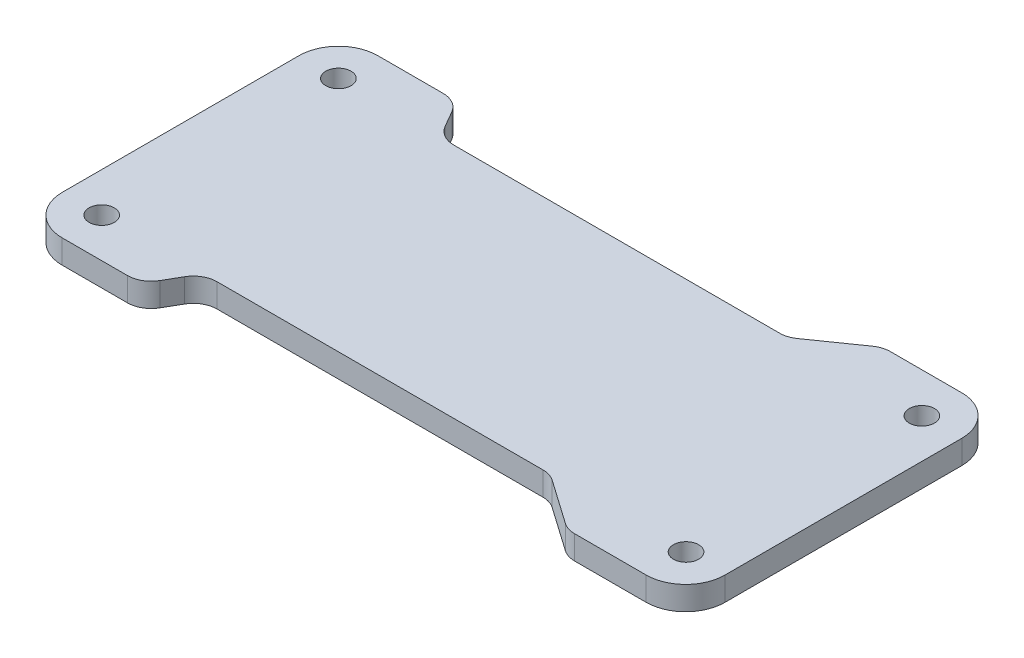
SolidWorks part; units mm, degrees
ref_plane "Front Plane" through (0, 0, 0) normal (0, 0, 1) x (1, 0, 0)
ref_plane "Top Plane" through (0, 0, 0) normal (0, 1, 0) x (1, 0, 0)
ref_plane "Right Plane" through (0, 0, 0) normal (1, 0, 0) x (0, 0, -1)
sketch "Sketch1" plane through (0, 53, 0) normal (0, 1, 0) x (1, 0, 0)
  line L8 (42, -14.9441) -> (42, 14.9441) construction
  line L9 (-37, 20) -> (37, 20)
  line L10 (-42, 15) -> (-42, -15)
  line L11 (-37, -20) -> (37, -20)
  line L12 (42, 15) -> (42, -15)
  line L13 (-42, 15) -> (-42, -15) construction
  line L14 (-3.2304, -20) -> (4.6447, -20) construction
  line L15 (-35.7279, 20) -> (-37, 20) construction
  arc A12 (37, 20) -> (42, 15) centre (37, 15) cw
  arc A13 (37, -20) -> (42, -15) centre (37, -15) ccw
  arc A14 (-42, -15) -> (-37, -20) centre (-37, -15) ccw
  arc A15 (-37, 20) -> (-42, 15) centre (-37, 15) ccw
  circle A17 centre (37, 14.9441) radius 1.6 construction
  circle A18 centre (37, 14.9441) radius 1.6
  circle A19 centre (37, -14.9441) radius 1.6 construction
  circle A20 centre (37, -14.9441) radius 1.6
  circle A21 centre (-37, -15) radius 1.6 construction
  circle A22 centre (-37, -15) radius 1.6
  circle A23 centre (-37, 15) radius 1.6 construction
  circle A24 centre (-37, 15) radius 1.6
  dimension "D1" = 0
  dimension "D5" = 5
  dimension "D2" = 0
  dimension "D3" = 0
  dimension "D4" = 0
extrude "Boss-Extrude1" add sketch "Sketch1" along normal blind 3
sketch "Sketch2" plane through (0, 56, 0) normal (0, 1, 0) x (1, 0, 0)
  line L0 (-27, 20) -> (-24.1132, 15)
  line L1 (37, 20) -> (-37, 20) construction
  line L2 (-24.1132, 15) -> (19.8593, 15)
  line L3 (19.8593, 15) -> (27, 20)
  line L4 (-27, 20) -> (27, 20)
  line L5 (42, -15) -> (42, 15) construction
  line L6 (-42, 15) -> (-42, -15) construction
  line L7 (-42, 0) -> (42, 0) construction
  line L8 (-27, -20) -> (27, -20)
  line L9 (19.8593, -15) -> (27, -20)
  line L10 (-24.1132, -15) -> (19.8593, -15)
  line L11 (-27, -20) -> (-24.1132, -15)
  dimension "D1" = 35
  dimension "D2" = 60
  dimension "D3" = 5
  dimension "D4" = 15
  dimension "D5" = 15
extrude "Cut-Extrude1" cut sketch "Sketch2" against normal up to surface (3 mm away) up to face at (-37, 53, 16.6)
fillet "Fillet1" radius 3 8 edges at (19.8593, 54.5, -15) (27, 54.5, -20) (-27, 54.5, -20) (-24.1132, 54.5, -15) (-27, 54.5, 20) (-24.1132, 54.5, 15) (19.8593, 54.5, 15) (27, 54.5, 20)
